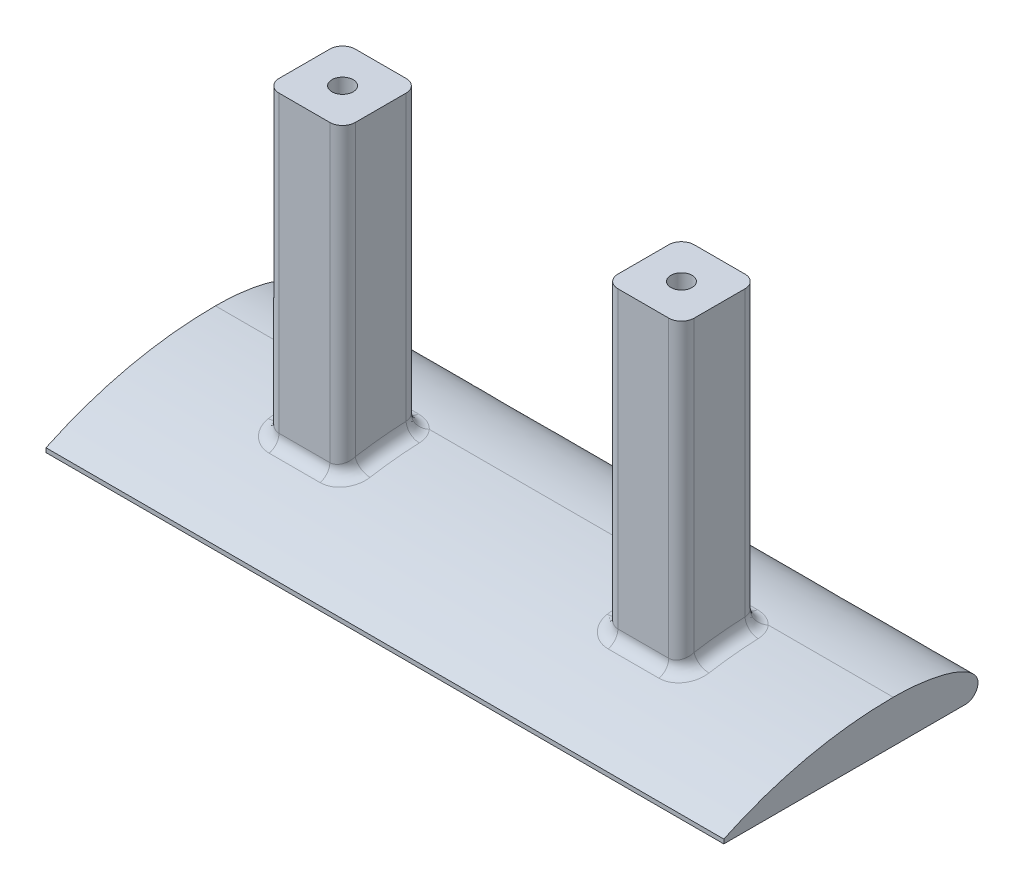
SolidWorks part; units mm, degrees
ref_plane "Front Plane" through (0, 0, 0) normal (0, 0, 1) x (1, 0, 0)
ref_plane "Top Plane" through (0, 0, 0) normal (0, 1, 0) x (1, 0, 0)
ref_plane "Right Plane" through (0, 0, 0) normal (1, 0, 0) x (0, 0, -1)
sketch "Sketch1" plane through (0, 0, 0) normal (1, 0, 0) x (0, 0, -1)
  line L0 (-15, 0) -> (13.5, 0)
  line L1 (-15, 0) -> (-15, 0.5)
  line L3 (15, 0) -> (15, 5) construction
  line L5 (-15, 5) -> (-15, 0.5) construction
  line L6 (13.5, 0) -> (15, 0) construction
  line L7 (-15, 5) -> (5, 5) construction
  line L8 (5, 5) -> (15, 5) construction
  arc A0 (13.5, 0) -> (15, 1.5) centre (13.5, 1.5) ccw
  arc A1 (5, 5) -> (-15, 0.5) centre (5, -41.6944) ccw
  ellipse E1 centre (5, 1.5) end of major axis (-5, 1.5) minor radius 3.5 (15, 1.5) -> (5, 5) ccw
  dimension "D2" = 3
  dimension "D5" = 10
  dimension "D1" = 0.5
  dimension "D3" = 5
  dimension "D4" = 30
  dimension "D6" = 15
extrude "Boss-Extrude1" add sketch "Sketch1" along normal mid plane 80
sketch "Sketch2" plane through (0, 0, 0) normal (0, -1, 0) x (-1, 0, 0)
  line L1 (24.5, 4.5) -> (15.5, 4.5)
  line L2 (24.5, 4.5) -> (24.5, -4.5)
  line L3 (24.5, -4.5) -> (15.5, -4.5)
  line L4 (15.5, 4.5) -> (15.5, -4.5)
  line L5 (24.5, 4.5) -> (15.5, -4.5) construction
  line L6 (24.5, -4.5) -> (15.5, 4.5) construction
  line L8 (-24.5, 4.5) -> (-15.5, 4.5)
  line L9 (-24.5, 4.5) -> (-24.5, -4.5)
  line L10 (-24.5, -4.5) -> (-15.5, -4.5)
  line L11 (-15.5, 4.5) -> (-15.5, -4.5)
  line L12 (-24.5, 4.5) -> (-15.5, -4.5) construction
  line L13 (-24.5, -4.5) -> (-15.5, 4.5) construction
  line L14 (-20, 0) -> (20, 0) construction
  point P4 (20, 0)
  point P11 (-20, 0)
  point P13 (0, 0)
  dimension "D1" = 9
  dimension "D3" = 40
extrude "Boss-Extrude2" add sketch "Sketch2" against normal blind 40
sketch "Sketch3" plane through (0, 40, 0) normal (0, 1, 0) x (1, 0, 0)
  line L0 (-24.5, 4.5) -> (-15.5, 4.5) construction
  line L1 (15.5, 4.5) -> (24.5, 4.5) construction
  circle A0 centre (-20, 0) radius 1.25
  circle A1 centre (20, 0) radius 1.25
  point P9 (-20, 4.5)
  point P13 (20, 4.5)
  dimension "D1" = 2.5
extrude "Cut-Extrude1" cut sketch "Sketch3" against normal blind 10
fillet "Fillet1" radius 1.5 8 edges at (-24.5, 22.4987, -4.5) (-15.5, 22.4987, -4.5) (15.5, 22.4987, -4.5) (24.5, 22.4987, -4.5) (24.5, 22.0117, 4.5) (15.5, 22.0117, 4.5) (-15.5, 22.0117, 4.5) (-24.5, 22.0117, 4.5)
fillet "Fillet2" radius 1.5 16 edges at (24.1616, 4.1344, 3.949) (24.5, 4.7304, 0.0105) (23.937, 4.9926, -4.1714) (20, 4.9973, -4.5) (15.8287, 4.9879, -3.937) (15.5, 4.7304, 0.0105) (16.0771, 4.0882, 4.1825) (-15.8384, 4.1344, 3.949) (-15.5, 4.7304, 0.0105) (-16.063, 4.9926, -4.1714) (-20, 4.9973, -4.5) (-24.1713, 4.9879, -3.937) (-24.5, 4.7304, 0.0105) (-23.9229, 4.0882, 4.1825) (20, 4.0234, 4.5) (-20, 4.0234, 4.5)
